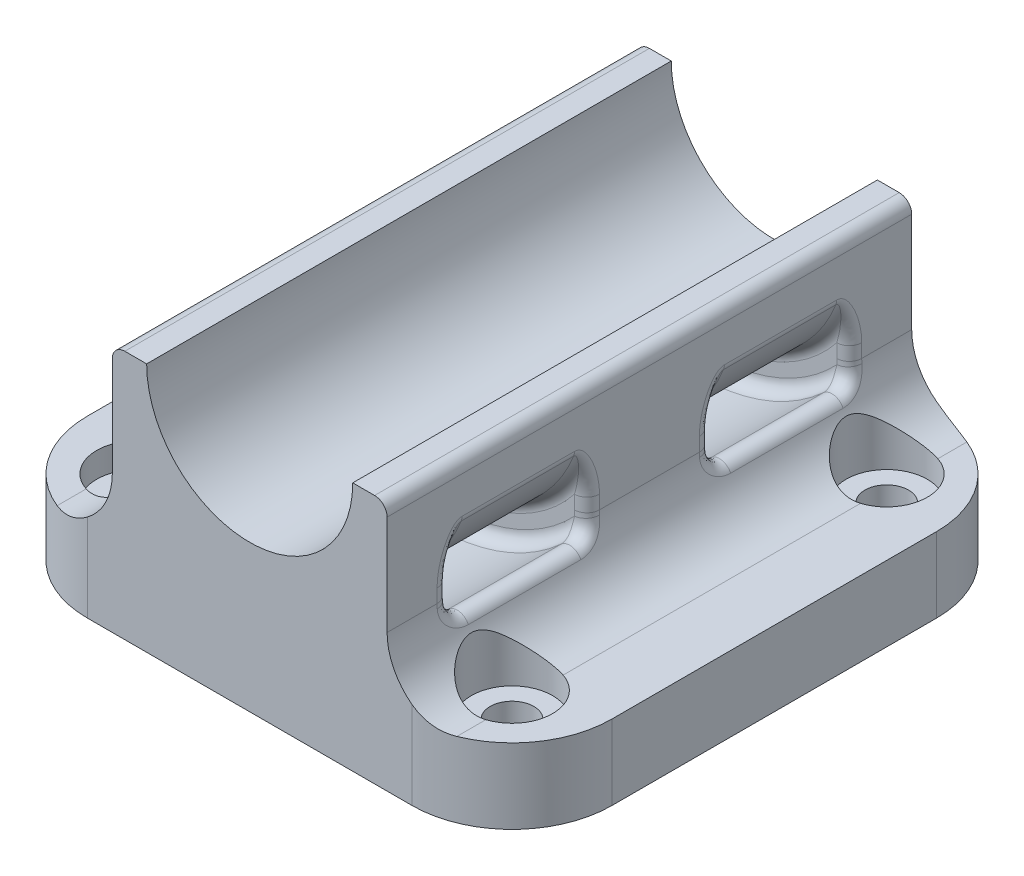
SolidWorks part; units mm, degrees
ref_plane "Спереди" through (0, 0, 0) normal (0, 0, 1) x (1, 0, 0)
ref_plane "Сверху" through (0, 0, 0) normal (0, 1, 0) x (1, 0, 0)
ref_plane "Справа" through (0, 0, 0) normal (1, 0, 0) x (0, 0, -1)
sketch "Эскиз1" plane through (0, 0, 0) normal (0, 1, 0) x (1, 0, 0)
  line L0 (-21, 0) -> (21, 0)
  line L1 (13, 21) -> (-13, 21)
  line L2 (21, 13) -> (21, -13)
  line L3 (13, -21) -> (-13, -21)
  line L4 (-21, 13) -> (-21, -13)
  line L5 (21, 21) -> (-21, -21) construction
  line L6 (21, -21) -> (-21, 21) construction
  line L7 (15, 15) -> (-15, 15) construction
  line L8 (15, 15) -> (15, -15) construction
  line L9 (15, -15) -> (-15, -15) construction
  line L10 (-15, 15) -> (-15, -15) construction
  line L11 (15, 15) -> (-15, -15) construction
  line L12 (15, -15) -> (-15, 15) construction
  arc A0 (-13, -21) -> (-21, -13) centre (-13, -13) cw
  arc A1 (21, -13) -> (13, -21) centre (13, -13) cw
  arc A2 (21, 13) -> (13, 21) centre (13, 13) ccw
  arc A3 (-13, 21) -> (-21, 13) centre (-13, 13) ccw
  circle A4 centre (-15, 15) radius 1.75 construction
  circle A8 centre (15, 15) radius 1.75 construction
  circle A9 centre (15, -15) radius 1.75 construction
  circle A10 centre (-15, -15) radius 1.75 construction
  circle A11 centre (0, 0) radius 21.2132 construction
  point P0 (0, 0)
  point P18 (0, 0)
  dimension "D3" = 8
  dimension "D5" = 3.5
  dimension "D1" = 42
  dimension "D2" = 42
  dimension "D4" = 30
  dimension "D6" = 4
extrude "Бобышка-Вытянуть1" add sketch "Эскиз1" along normal blind 6 contours L1 A3 L4 L0 L2 A2 A8 A4 region at (0, 0, -10.2199)
sketch "Эскиз2" plane through (0, 6, 0) normal (0, 1, 0) x (1, 0, 0)
  line L0 (-21, 0) -> (21, 0) construction
  line L1 (11, 21) -> (-11, 21)
  line L2 (11, 21) -> (11, 0)
  line L3 (11, 0) -> (-11, 0)
  line L4 (-11, 21) -> (-11, 0)
  line L5 (11, 21) -> (-11, 0) construction
  line L6 (11, 0) -> (-11, 21) construction
  line L7 (13, 21) -> (-13, 21) construction
  point P0 (0, 10.5)
  dimension "D1" = 22
extrude "Бобышка-Вытянуть2" add sketch "Эскиз2" along normal blind 14
ref_plane "Плоскость1" through (0, 0, -10.5) normal (0, 0, 1) x (1, 0, 0)
sketch "Эскиз3" plane through (0, 0, 0) normal (0, 0, 1) x (1, 0, 0)
  line L0 (-11, 20) -> (11, 20) construction
  circle A0 centre (0, 20) radius 8.25
  dimension "D1" = 16.5
extrude "Вырез-Вытянуть1" cut sketch "Эскиз3" against normal through all
sketch "Эскиз4" plane through (0, 0, -10.5) normal (0, 0, 1) x (1, 0, 0)
  circle A0 centre (0, 20) radius 11.75
  circle A1 centre (0, 20) radius 14.75
  arc A2 (-8.25, 20) -> (8.25, 20) centre (0, 20) ccw construction
  dimension "D2" = 3.5
extrude "Вырез-Вытянуть2" cut sketch "Эскиз4" against normal mid plane 11
fillet "Скругление2" radius 5 2 edges at (-11, 6, -10.5) (11, 6, -10.5)
fillet "Скругление3" radius 1 18 edges at (11.0146, 10.6184, -16) (11, 13.4347, -16) (11.0583, 10.239, -10.5) (-11.0583, 10.239, -10.5) (11, 15.8693, -10.5) (-11, 15.8693, -10.5) (11.0146, 10.6184, -5) (-11.0146, 10.6184, -5) (-11.0146, 10.6184, -16) (11, 13.4347, -5) (0, 5.25, -5) (0, 8.25, -5) (-11, 13.4347, -5) (-11, 13.4347, -16) (0, 8.25, -16) (0, 5.25, -16) (11, 20, -10.5) (-11, 20, -10.5)
sketch "Эскиз6" plane through (0, 6, 0) normal (0, 1, 0) x (1, 0, 0)
  line L1 (15, -15) -> (-15, -15) construction
  line L2 (15, -15) -> (15, 15) construction
  line L3 (15, 15) -> (-15, 15) construction
  line L4 (-15, -15) -> (-15, 15) construction
  line L5 (15, -15) -> (-15, 15) construction
  line L6 (15, 15) -> (-15, -15) construction
  circle A0 centre (-15, 15) radius 1.75
  circle A1 centre (15, 15) radius 1.75
  point P0 (0, 0)
  dimension "D3" = 3.5
  dimension "D4" = 3.5
  dimension "D1" = 30
  dimension "D2" = 30
extrude "Вырез-Вытянуть4" cut sketch "Эскиз6" against normal through all both and the other way through all
sketch "Эскиз7" plane through (0, 6, 0) normal (0, 1, 0) x (1, 0, 0)
  circle A0 centre (-15, 15) radius 3.25
  circle A1 centre (15, 15) radius 3.25
  dimension "D1" = 6.5
  dimension "D2" = 6.5
extrude "Вырез-Вытянуть5" cut sketch "Эскиз7" along normal through all and the other way offset from surface 4 other way up to face at (-15, 0, -13.25)
mirror "Зеркальное отражение1" about plane through (0, 6, 0) normal (0, 0, -1) of bodies 109
equation "\"print_offset\"= 0.5"
equation "\"screw_m5_d\"= 4"
equation "\"screw_m5_hh_d\"= 7"
equation "\"nut_m5_d\"= 7.9"
equation "\"nut_m5_h\"= 3.9"
equation "\"tube_d\"= 16"
equation "\"tube_tape_d\"= 3"
equation "\"tube_tape_h\"= 11"
equation "\"D5@Эскиз1\"=\"print_offset\"+3"
equation "\"D1@Эскиз3\"=\"tube_d\"+\"print_offset\""
equation "\"D1@Эскиз4\"=\"tube_tape_d\""
equation "\"D1@Вырез-Вытянуть2\"=\"tube_tape_h\""
equation "\"D4@Эскиз6\"=\"D3@Эскиз6\""
equation "\"D1@Эскиз7\"=6.5"
equation "\"D2@Эскиз7\"=\"D1@Эскиз7\""
